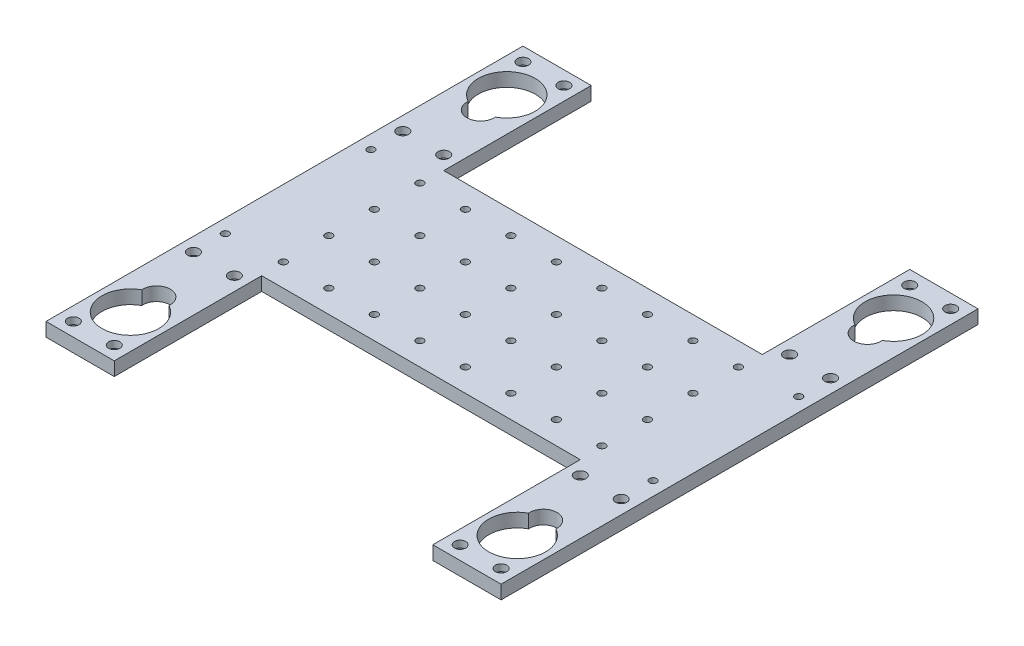
SolidWorks part; units mm, degrees
ref_plane "前视基准面" through (0, 0, 0) normal (0, 0, 1) x (1, 0, 0)
ref_plane "上视基准面" through (0, 0, 0) normal (0, 1, 0) x (1, 0, 0)
ref_plane "右视基准面" through (0, 0, 0) normal (1, 0, 0) x (0, 0, -1)
other "Configuration Table"
sketch "草图1" plane through (0, 0, 0) normal (0, 1, 0) x (1, 0, 0)
  line L1 (0, 0) -> (100, 0)
  line L2 (0, 0) -> (0, -40)
  line L3 (0, -40) -> (100, -40)
  line L4 (100, 0) -> (100, -40)
  line L5 (0, 0) -> (15, 0)
  line L6 (0, 0) -> (0, 32.4)
  line L7 (0, 32.4) -> (15, 32.4)
  line L8 (15, 0) -> (15, 32.4)
  line L11 (100, 0) -> (85, 0)
  line L12 (100, 0) -> (100, 32.4)
  line L13 (100, 32.4) -> (85, 32.4)
  line L14 (85, 0) -> (85, 32.4)
  line L15 (0, -40) -> (15, -40)
  line L16 (0, -40) -> (0, -72.4)
  line L17 (0, -72.4) -> (15, -72.4)
  line L18 (15, -40) -> (15, -72.4)
  line L19 (100, -40) -> (85, -40)
  line L20 (100, -40) -> (100, -72.4)
  line L21 (100, -72.4) -> (85, -72.4)
  line L22 (85, -40) -> (85, -72.4)
  dimension "D1" = 40
  dimension "D2" = 100
  dimension "D3" = 32.4
  dimension "D4" = 15
extrude "凸台-拉伸1" add sketch "草图1" along normal blind 3 contours L2 L3 L4 L1 | L6 L7 L8 L5 | L11 L14 L13 L12 | L15 L18 L17 L16 | L19 L22 L21 L20
sketch "草图2" plane through (0, 0, 0) normal (0, -1, 0) x (1, 0, 0)
  line L0 (0, -32.4) -> (0, 72.4) construction
  line L1 (0, -32.4) -> (15, -32.4) construction
  line L2 (15, 0) -> (85, 0) construction
  line L3 (15, 0) -> (15, -32.4) construction
  line L4 (100, 72.4) -> (85, 72.4) construction
  line L5 (7.5, -21.35) -> (7.5, -15.6) construction
  line L6 (92.5, 55.6) -> (92.5, 61.35) construction
  line L8 (15, 40) -> (85, 40) construction
  line L9 (85, 40) -> (85, 72.4) construction
  line L10 (100, -32.4) -> (100, 72.4) construction
  circle A0 centre (7.5, -21.35) radius 6.25
  circle A1 centre (3, -29.4) radius 2
  circle A2 centre (3, -3) radius 2
  circle A3 centre (12, -3) radius 2
  circle A4 centre (12, -29.4) radius 2
  circle A5 centre (3, -3) radius 1.25
  circle A6 centre (12, -3) radius 1.25
  circle A7 centre (12, -29.4) radius 1.25
  circle A8 centre (3, -29.4) radius 1.25
  circle A9 centre (7.5, -15.6) radius 3
  circle A10 centre (92.5, -21.35) radius 6.25
  circle A12 centre (92.5, -15.6) radius 3
  circle A13 centre (88, -3) radius 2
  circle A14 centre (88, -3) radius 1.25
  circle A15 centre (97, -3) radius 2
  circle A16 centre (97, -3) radius 1.25
  circle A17 centre (88, -29.4) radius 2
  circle A18 centre (88, -29.4) radius 1.25
  circle A19 centre (97, -29.4) radius 2
  circle A20 centre (97, -29.4) radius 1.25
  circle A21 centre (92.5, 61.35) radius 6.25
  circle A22 centre (92.5, 55.6) radius 3
  circle A23 centre (88, 69.4) radius 2
  circle A24 centre (88, 69.4) radius 1.25
  circle A25 centre (97, 69.4) radius 2
  circle A26 centre (97, 69.4) radius 1.25
  circle A27 centre (88, 43) radius 2
  circle A28 centre (88, 43) radius 1.25
  circle A29 centre (97, 43) radius 2
  circle A30 centre (97, 43) radius 1.25
  circle A31 centre (3, 69.4) radius 2
  circle A32 centre (3, 69.4) radius 1.25
  circle A33 centre (12, 69.4) radius 2
  circle A34 centre (12, 69.4) radius 1.25
  circle A35 centre (7.5, 61.35) radius 6.25
  circle A36 centre (7.5, 55.6) radius 3
  circle A37 centre (3, 43) radius 2
  circle A38 centre (3, 43) radius 1.25
  circle A39 centre (12, 43) radius 2
  circle A40 centre (12, 43) radius 1.25
  point P59 (92.5, 72.4)
  dimension "D7" = 4
  dimension "D8" = 12.5
  dimension "D9" = 2.5
  dimension "D11" = 6
  dimension "D1" = 7.5
  dimension "D2" = 11.05
  dimension "D3" = 3
  dimension "D4" = 3
  dimension "D5" = 3
  dimension "D6" = 3
  dimension "D10" = 5.75
  dimension "D12" = 11.05
  dimension "D13" = 3
  dimension "D14" = 3
  dimension "D15" = 3
  dimension "D16" = 3
extrude "切除-拉伸1" cut sketch "草图2" against normal through all contours A5 | A8 | A7 | A6 | A0 | A9 | A35 | A36 | A32 | A38 | A40 | A34 | A24 | A26 | A22 | A21 | A28 | A30 | A14 | A16 | A10 | A12 | A18 | A20
extrude "切除-拉伸2" cut sketch "草图2<3>" against normal blind 1.5 contours A1 | A2 | A3 | A4 | A17 | A19 | A13 | A15 | A31 | A33 | A37 | A39 | A23 | A25 | A27 | A29
sketch "草图2<3>" plane through (0, 0, 0) normal (0, -1, 0) x (1, 0, 0) same geometry as "草图2"
sketch "草图4" plane through (0, 3, 0) normal (0, 1, 0) x (1, 0, 0)
  line L1 (0, 32.4) -> (0, -72.4) construction
  line L2 (15, 0) -> (85, 0) construction
  line L3 (15, -40) -> (85, -40) construction
  line L4 (100, 32.4) -> (100, -72.4) construction
  circle A0 centre (3, -4) radius 0.8
  circle A1 centre (3, -36) radius 0.8
  circle A2 centre (97, -36) radius 0.8
  circle A3 centre (97, -4) radius 0.8
  dimension "D1" = 1.6
  dimension "D2" = 3
  dimension "D3" = 4
  dimension "D4" = 4
  dimension "D5" = 3
extrude "切除-拉伸3" cut sketch "草图4" against normal through all contours A1 | A0 | A3 | A2
sketch "草图5" plane through (0, 3, 0) normal (0, 1, 0) x (1, 0, 0)
  line L0 (14.75, -5) -> (-0.5, -5) construction
  line L1 (-0.5, -40.5) -> (-0.5, 0.5) construction
  line L2 (14.75, -5) -> (14.75, 0) construction
  line L3 (84.75, -40) -> (84.75, -35) construction
  line L4 (15, 0) -> (85, 0) construction
  line L5 (15, -40) -> (85, -40) construction
  line L7 (84.75, -35) -> (100, -35) construction
  line L9 (100, 32.4) -> (100, -72.4) construction
  circle A0 centre (14.75, -5) radius 0.8
  circle A36 centre (24.75, -5) radius 0.8
  circle A37 centre (34.75, -5) radius 0.8
  circle A38 centre (44.75, -5) radius 0.8
  circle A39 centre (54.75, -5) radius 0.8
  circle A40 centre (64.75, -5) radius 0.8
  circle A41 centre (74.75, -5) radius 0.8
  circle A42 centre (84.75, -5) radius 0.8
  circle A43 centre (24.75, -15) radius 0.8
  circle A44 centre (34.75, -15) radius 0.8
  circle A45 centre (44.75, -15) radius 0.8
  circle A46 centre (54.75, -15) radius 0.8
  circle A47 centre (64.75, -15) radius 0.8
  circle A48 centre (74.75, -15) radius 0.8
  circle A49 centre (84.75, -15) radius 0.8
  circle A50 centre (24.75, -25) radius 0.8
  circle A51 centre (34.75, -25) radius 0.8
  circle A52 centre (44.75, -25) radius 0.8
  circle A53 centre (54.75, -25) radius 0.8
  circle A54 centre (64.75, -25) radius 0.8
  circle A55 centre (74.75, -25) radius 0.8
  circle A56 centre (84.75, -25) radius 0.8
  circle A57 centre (24.75, -35) radius 0.8
  circle A58 centre (34.75, -35) radius 0.8
  circle A59 centre (44.75, -35) radius 0.8
  circle A60 centre (54.75, -35) radius 0.8
  circle A61 centre (64.75, -35) radius 0.8
  circle A62 centre (74.75, -35) radius 0.8
  circle A63 centre (84.75, -35) radius 0.8
  circle A64 centre (14.75, -15) radius 0.8
  circle A65 centre (14.75, -25) radius 0.8
  circle A66 centre (14.75, -35) radius 0.8
  dimension "D1" = 1.6
  dimension "D2" = 8
  dimension "D3" = 4
extrude "切除-拉伸4" cut sketch "草图5" against normal blind 3
